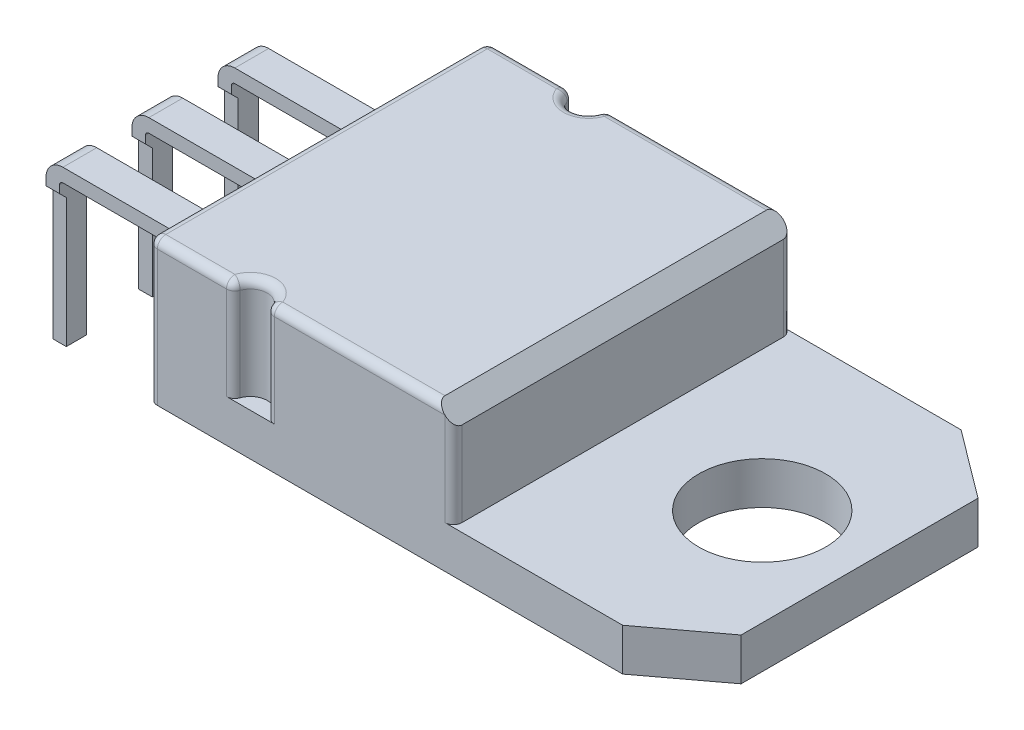
SolidWorks part; units mm, degrees
ref_plane "前视基准面" through (0, 0, 0) normal (0, 0, 1) x (1, 0, 0)
ref_plane "上视基准面" through (0, 0, 0) normal (0, 1, 0) x (1, 0, 0)
ref_plane "右视基准面" through (0, 0, 0) normal (1, 0, 0) x (0, 0, -1)
sketch "草图1" plane through (0, 0, 0) normal (0, 1, 0) x (1, 0, 0)
  line L0 (0, 0) -> (14, 0)
  line L1 (16, 1.5) -> (16, 8.5)
  line L2 (14, 0) -> (16, 1.5)
  line L3 (0, 10) -> (0, 0)
  line L4 (0, 5) -> (26.25, 5) construction
  line L5 (15, 12.0634) -> (15, -4.1334) construction
  line L8 (14, 10) -> (16, 8.5)
  line L9 (14, 10) -> (0, 10)
  circle A0 centre (13.125, 5) radius 1.875
  dimension "D3" = 3.75
  dimension "D2" = 10
  dimension "D4" = 1
extrude "凸台-拉伸1" add sketch "草图1" along normal blind 1.25
sketch "草图2" plane through (0, 1.25, 0) normal (0, 1, 0) x (1, 0, 0)
  line L0 (0, 10) -> (2.5, 10)
  line L1 (14, 10) -> (0, 10) construction
  line L2 (9, 10) -> (9, 0)
  line L3 (0, 0) -> (14, 0) construction
  line L4 (9, 0) -> (3.5, 0)
  line L5 (0, 0) -> (0, 10)
  line L6 (3, 10) -> (3, 0) construction
  line L7 (2.5, 0) -> (0, 0)
  line L8 (0, 5) -> (9, 5) construction
  line L9 (3.5, 10) -> (9, 10)
  arc A0 (3.5, 0) -> (2.5, 0) centre (3, 0) ccw
  arc A1 (3.5, 10) -> (2.5, 10) centre (3, 10) cw
  dimension "D3" = 1
  dimension "D1" = 9
  dimension "D2" = 3
extrude "凸台-拉伸2" add sketch "草图2" along normal blind 3
fillet "圆角1" radius 0.25 15 edges at (0, 2.125, -10) (6.25, 4.25, -10) (3, 4.25, -9.5) (1.25, 4.25, -10) (0, 4.25, -5) (0, 2.125, 0) (1.25, 4.25, 0) (3, 4.25, -0.5) (6.25, 4.25, 0)
chamfer "倒角1" distance 0.5 angle 45 1 edges at (9, 4.25, -5)
sketch "草图3" plane through (0, 0, 0) normal (-1, 0, 0) x (0, 0, 1)
  line L0 (-10.84, 2.54) -> (2.0042, 2.54) construction
  line L1 (-9.75, 0) -> (-0.25, 0) construction
  line L2 (-5, 4) -> (-5, 0) construction
  line L3 (-0.25, 4) -> (-9.75, 4) construction
  line L4 (-5.4998, 2.74) -> (-5.4998, 2.34)
  line L5 (-5.4998, 2.74) -> (-4.5002, 2.74)
  line L6 (-5.4998, 2.34) -> (-4.5002, 2.34)
  line L7 (-4.5002, 2.74) -> (-4.5002, 2.34)
  line L12 (0.84, 2.54) -> (-12.0042, 2.54) construction
  point P9 (-4.5002, 2.54)
  point P12 (-5, 2.74)
  point P15 (-5.4998, 2.54)
  dimension "D1" = 2.54
  dimension "D2" = 0.4
  dimension "D3" = 0.9997
ref_plane "基准面1" through (0, 0, -5) normal (0, 0, -1) x (-1, 0, 0)
sketch "草图4" plane through (0, 0, -5) normal (0, 0, -1) x (-1, 0, 0)
  line L0 (0, 2.74) -> (4.5, 2.74)
  line L1 (5, 2.24) -> (5, -2)
  line L2 (-5.5262, -2) -> (2.8634, -2) construction
  line L3 (-14, 0) -> (-0.25, 0) construction
  arc A0 (5, 2.24) -> (4.5, 2.74) centre (4.5, 2.24) ccw
  point P10 (5, 2.74)
  dimension "D3" = 0.5
  dimension "D1" = 5
  dimension "D2" = 2
sweep "扫描1" add profiles "草图3" path "草图4"
sketch "草图5" plane through (-5, 0, 0) normal (-1, 0, 0) x (0, 0, 1)
  line L0 (-5, -2) -> (-5, 2.2196) construction
  line L1 (-4.5002, -2) -> (-5.4998, -2) construction
  line L2 (-5, 2.2) -> (-5, -2.2) construction
  line L6 (-4.7, 1.8147) -> (-4.7, -2)
  line L8 (-5.3, 1.8147) -> (-5.3, -2)
  line L9 (-5.3, 1.8147) -> (-5.4998, 2.0145)
  line L10 (-5.4998, 2.24) -> (-5.4998, -2) construction
  line L12 (-4.5002, 2.24) -> (-4.5002, -2) construction
  line L13 (-4.5002, 2.0145) -> (-4.7, 1.8147)
  line L14 (-5.4998, 2.0145) -> (-5.4998, -2)
  line L15 (-5.4998, -2) -> (-5.3, -2)
  line L16 (-4.5002, 2.0145) -> (-4.5002, -2)
  line L17 (-4.5002, -2) -> (-4.7, -2)
  point P8 (-5, 1.8147)
  dimension "D1" = 0.6
extrude "切除-拉伸1" cut sketch "草图5" against normal up to next
pattern_linear "阵列(线性)1" count 2 spacing 2.54 along (0, 0, 1) of "切除-拉伸1", "扫描1"
mirror "镜向1" about plane through (0, 0, -5) normal (0, 0, -1) of "阵列(线性)1", "扫描1", "切除-拉伸1"
